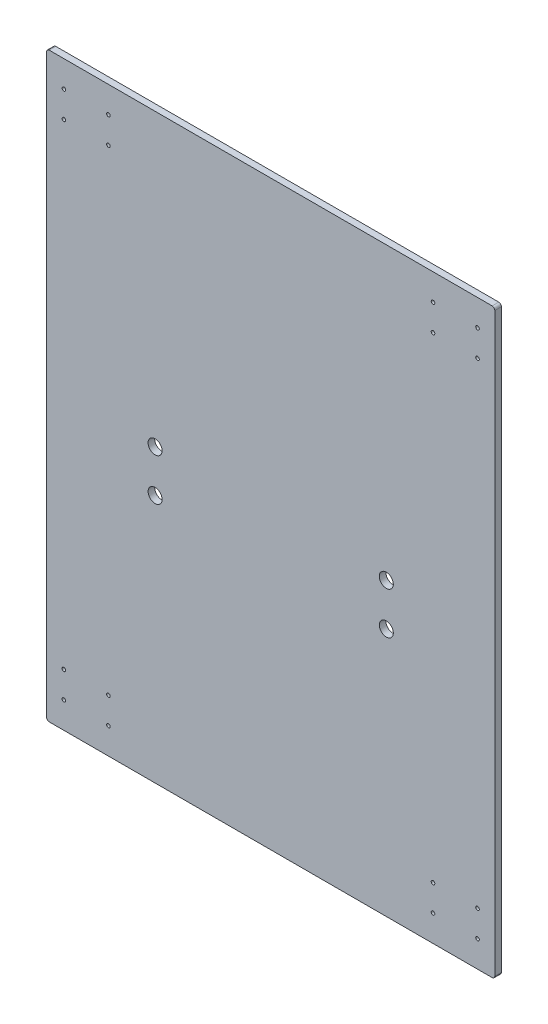
SolidWorks part; units mm, degrees
material "Plain Carbon Steel"
ref_plane "Front Plane" through (0, 0, 0) normal (0, 0, 1) x (1, 0, 0)
ref_plane "Top Plane" through (0, 0, 0) normal (0, 1, 0) x (1, 0, 0)
ref_plane "Right Plane" through (0, 0, 0) normal (1, 0, 0) x (0, 0, -1)
sketch "Sketch1" plane through (0, 0, 0) normal (0, 0, 1) x (1, 0, 0)
  line L1 (0, 0) -> (0, 38.1) construction
  line L2 (393.7, -522.3669) -> (-38.1, -522.3669)
  line L3 (393.7, -522.3669) -> (393.7, 38.1)
  line L4 (393.7, 38.1) -> (-38.1, 38.1)
  line L5 (-38.1, -522.3669) -> (-38.1, 38.1)
  line L6 (393.7, -522.3669) -> (-38.1, 38.1) construction
  line L7 (393.7, 38.1) -> (-38.1, -522.3669) construction
  line L9 (0, 0) -> (-38.1, 0) construction
  line L10 (-25.4, -21.4312) -> (-25.4, 21.4312) construction
  point P4 (177.8, -242.1334)
  dimension "D1" = 12.7
extrude "Boss-Extrude1" add sketch "Sketch1" along normal blind 6.35
fillet "Fillet1" radius 2.54 4 edges at (393.7, 38.1, 3.175) (393.7, -522.3669, 3.175) (-38.1, -522.3669, 3.175) (-38.1, 38.1, 3.175)
sketch "Sketch3" plane through (0, 0, 0) normal (0, 0, -1) x (-1, 0, 0)
  line L0 (-177.8, 38.1) -> (-177.8, -522.3669) construction
  line L1 (-391.16, 38.1) -> (35.56, 38.1) construction
  line L2 (35.56, -522.3669) -> (-391.16, -522.3669) construction
  line L3 (-177.8, -262.14) -> (-289.1714, -262.14) construction
  line L4 (-289.1714, -241.82) -> (-289.1714, -282.46) construction
  point P8 (-289.1714, -241.82)
  point P9 (-289.1714, -282.46)
  point P13 (-66.4286, -282.46)
  point P14 (-66.4286, -241.82)
  dimension "D1" = 40.64
  dimension "D2" = 279.92
  dimension "D3" = 222.7428
hole_wizard "1/2 Clearance Hole1" positions "Sketch3" profile "Sketch4" hole size "1/2" standard "ANSI Inch" end condition up to next
sketch "Sketch4" plane through (66.4286, -241.82, 0) normal (1, 0, 0) x (0, 1, 0)
  line L0 (0, 0) -> (0, 6.35)
  line L1 (0, 6.35) -> (6.7462, 6.35)
  line L2 (6.7462, 6.35) -> (6.7462, 0)
  line L5 (6.7462, 0) -> (0, 0)
  line L11 (0, -6.35) -> (0, 107.95) construction
  dimension "Thru Hole Dia." = 13.4925
  dimension "Thru Hole Depth" = 6.35
sketch "Sketch6" plane through (0, 0, 0) normal (0, 0, -1) x (-1, 0, 0)
  line L0 (-393.7, -519.8269) -> (-393.7, 35.56) construction
  line L1 (-391.16, 38.1) -> (35.56, 38.1) construction
  line L2 (-177.8, 38.1) -> (-177.8, -522.3669) construction
  line L3 (35.56, -522.3669) -> (-391.16, -522.3669) construction
  line L4 (38.1, -242.1334) -> (-393.7, -242.1334) construction
  line L5 (38.1, 35.56) -> (38.1, -519.8269) construction
  point P0 (-377.0376, 12.7)
  point P1 (-377.0376, -12.7)
  point P2 (-334.1624, 12.7)
  point P3 (-334.1624, -12.7)
  point P16 (-21.4376, -12.7)
  point P17 (21.4376, -12.7)
  point P18 (21.4376, 12.7)
  point P19 (-21.4376, 12.7)
  point P20 (-21.4376, -496.9669)
  point P21 (21.4376, -496.9669)
  point P22 (21.4376, -471.5669)
  point P23 (-21.4376, -471.5669)
  point P24 (-334.1624, -471.5669)
  point P25 (-334.1624, -496.9669)
  point P26 (-377.0376, -471.5669)
  point P27 (-377.0376, -496.9669)
  dimension "D1" = 16.6624
  dimension "D2" = 25.4
  dimension "D3" = 25.4
  dimension "D4" = 42.8752
hole_wizard "#5 Clearance Hole1" positions "Sketch6" profile "Sketch7" hole size "#5" standard "ANSI Inch" end condition up to next
sketch "Sketch7" plane through (377.0376, 12.7, 0) normal (1, 0, 0) x (0, 1, 0)
  line L0 (0, 0) -> (0, 6.35)
  line L1 (0, 6.35) -> (1.7272, 6.35)
  line L2 (1.7272, 6.35) -> (1.7272, 0)
  line L5 (1.7272, 0) -> (0, 0)
  line L11 (0, -6.35) -> (0, 107.95) construction
  dimension "Thru Hole Dia." = 3.4544
  dimension "Thru Hole Depth" = 6.35
